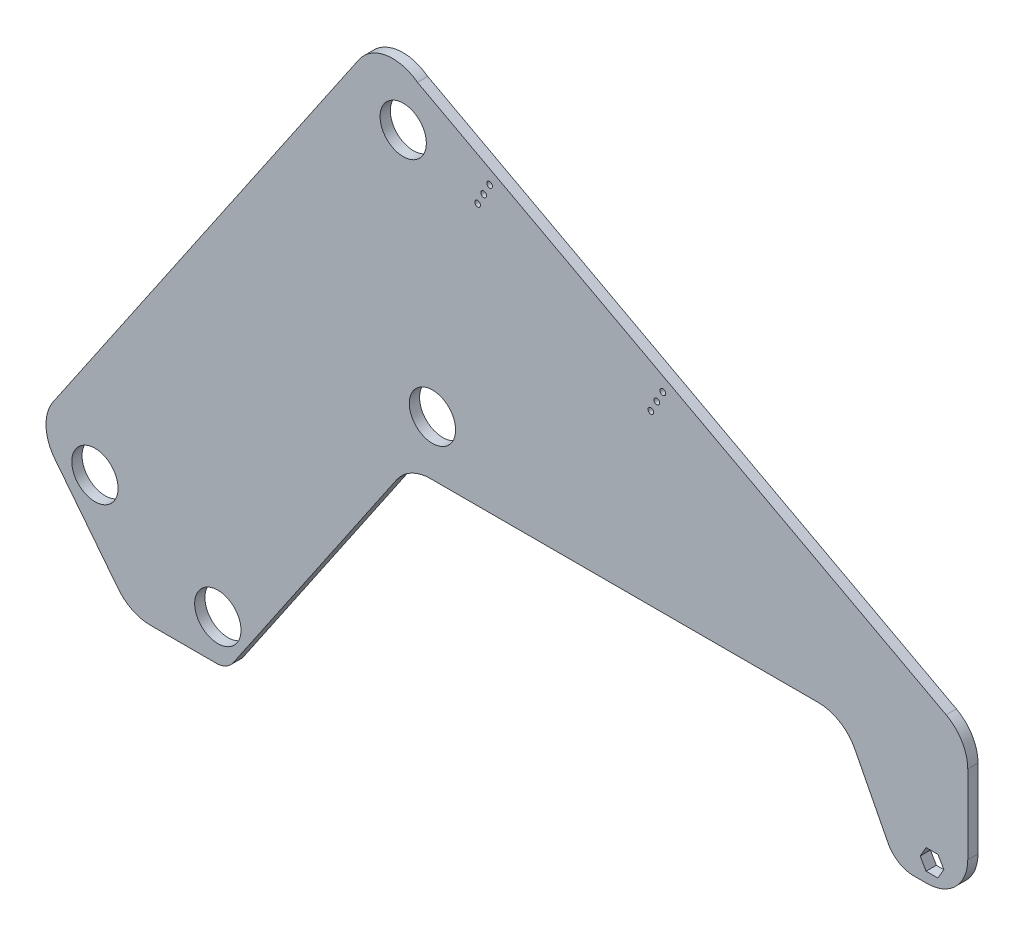
SolidWorks part; units mm, degrees
other "Markup1"
sketch "Sketch1" plane through (-441.7893, 331.8239, 6.35) normal (-0.0431, 0.0102, 0.999) x (0.9985, 0.0354, 0.0427)
sketch "Sketch2" plane through (-413.6701, 343.933, 6.35) normal (-0.0431, 0.0102, 0.999) x (0.9985, 0.0354, 0.0427)
sketch "Sketch3" plane through (-436.3774, 318.5567, 6.35) normal (-0.0431, 0.0102, 0.999) x (0.9985, 0.0354, 0.0427)
sketch "Sketch5" plane through (-436.3774, 318.5567, 6.35) normal (-0.0431, 0.0102, 0.999) x (0.9985, 0.0354, 0.0427)
sketch "Sketch7" plane through (-430.3226, 318.5567, 6.35) normal (-0.0431, 0.0102, 0.999) x (0.9985, 0.0354, 0.0427)
sketch "Sketch9" plane through (-430.3226, 318.5567, 6.35) normal (-0.0431, 0.0102, 0.999) x (0.9985, 0.0354, 0.0427)
sketch "Sketch11" plane through (-430.3226, 318.5567, 6.35) normal (-0.0431, 0.0102, 0.999) x (0.9985, 0.0354, 0.0427)
sketch "Sketch13" plane through (-430.3226, 318.5567, 6.35) normal (-0.0431, 0.0102, 0.999) x (0.9985, 0.0354, 0.0427)
sketch "Sketch15" plane through (-430.3226, 318.5567, 6.35) normal (-0.0431, 0.0102, 0.999) x (0.9985, 0.0354, 0.0427)
sketch "Sketch17" plane through (-430.3226, 318.5567, 6.35) normal (-0.0431, 0.0102, 0.999) x (0.9985, 0.0354, 0.0427)
sketch "Sketch19" plane through (-430.3226, 318.5567, 6.35) normal (-0.0431, 0.0102, 0.999) x (0.9985, 0.0354, 0.0427)
other "Markup2"
sketch "Sketch4" plane through (102.4721, 318.5567, 6.35) normal (0.9364, 0.1073, 0.3342) x (0.3416, -0.0598, -0.9379)
sketch "Sketch6" plane through (102.4721, 318.5567, 6.35) normal (0.9364, 0.1073, 0.3342) x (0.3416, -0.0598, -0.9379)
sketch "Sketch8" plane through (141.2086, 318.5567, 6.35) normal (0.9364, 0.1073, 0.3342) x (0.3416, -0.0598, -0.9379)
sketch "Sketch10" plane through (141.2086, 318.5567, 6.35) normal (0.9364, 0.1073, 0.3342) x (0.3416, -0.0598, -0.9379)
sketch "Sketch12" plane through (141.2086, 318.5567, 6.35) normal (0.9364, 0.1073, 0.3342) x (0.3416, -0.0598, -0.9379)
sketch "Sketch14" plane through (141.2086, 318.5567, 6.35) normal (0.9364, 0.1073, 0.3342) x (0.3416, -0.0598, -0.9379)
sketch "Sketch16" plane through (141.2086, 318.5567, 6.35) normal (0.9364, 0.1073, 0.3342) x (0.3416, -0.0598, -0.9379)
sketch "Sketch18" plane through (141.2086, 318.5567, 6.35) normal (0.9364, 0.1073, 0.3342) x (0.3416, -0.0598, -0.9379)
sketch "Sketch20" plane through (141.2086, 318.5567, 6.35) normal (0.9364, 0.1073, 0.3342) x (0.3416, -0.0598, -0.9379)
material "Lexan"
ref_plane "Front Plane" through (0, 0, 0) normal (0, 0, 1) x (1, 0, 0)
ref_plane "Top Plane" through (0, 0, 0) normal (0, 1, 0) x (1, 0, 0)
ref_plane "Right Plane" through (0, 0, 0) normal (1, 0, 0) x (0, 0, -1)
sketch "Model" plane through (0, 0, 0) normal (0, 0, 1) x (1, 0, 0)
  line L1 (-191.9011, 104.6502) -> (-112.96, 104.6502)
  line L3 (-314.2383, -55.3595) -> (-212.8994, 93.5413)
  line L4 (-236.3032, 307.4477) -> (-425.9209, 28.8361)
  line L5 (-424.8981, -1.1437) -> (-385.5815, -51.2028)
  line L13 (126.3831, 53.8502) -> (122.717, 60.2002)
  line L14 (122.717, 60.2002) -> (115.3846, 60.2002)
  line L15 (115.3846, 60.2002) -> (111.7185, 53.8502)
  line L16 (111.7185, 53.8502) -> (115.3846, 47.5002)
  line L17 (115.3846, 47.5002) -> (122.717, 47.5002)
  line L18 (122.717, 47.5002) -> (126.3831, 53.8502)
  line L19 (-365.606, -60.914) -> (-324.7375, -60.914)
  line L20 (-871.0211, -88.854) -> (370.1019, -88.854) construction
  line L22 (141.2086, 66.5502) -> (141.2086, 78.8846)
  line L27 (107.6196, 41.1502) -> (115.8086, 41.1502)
  line L28 (-399.9752, 2.586) -> (-323.7752, -35.514) construction
  line L29 (-323.7752, -35.514) -> (-190.7071, 138.5169) construction
  line L30 (-190.7071, 138.5169) -> (-208.8329, 283.4378) construction
  line L31 (-208.8329, 283.4378) -> (-399.9752, 2.586) construction
  line L32 (91.8004, 50.8135) -> (71.26, 90.8456)
  line L33 (48.6612, 104.6502) -> (-11.3966, 104.6502)
  line L34 (141.2086, 78.8846) -> (141.2086, 115.3033)
  line L35 (127.8091, 137.6897) -> (-86.3327, 252.4836)
  line L36 (-112.96, 104.6502) -> (-68.51, 104.6502)
  line L37 (-122.3008, 271.7648) -> (-85.2777, 251.9181)
  line L38 (-199.9496, 313.3896) -> (-46.986, 224.7627)
  line L39 (-46.986, 224.7627) -> (-44.2259, 229.9116)
  line L40 (-68.51, 104.6502) -> (-2.1388, 104.6502)
  line L41 (-122.3008, 271.7648) -> (-199.9496, 313.3896)
  line L42 (-51.0757, 217.1337) -> (-46.986, 224.7627)
  line L43 (-47.826, 223.1957) -> (-51.5462, 216.2559) construction
  line L44 (-199.9496, 313.3896) -> (-154.405, 282.3463)
  line L45 (-154.405, 282.3463) -> (-151.6449, 287.4952)
  line L46 (-154.405, 282.3463) -> (-156.7821, 277.912)
  line L47 (-155.2451, 280.7793) -> (-158.9652, 273.8395) construction
  arc A3 (121.2475, 59.8082) -> (121.352, 60.2002) centre (96.7586, 66.5502) ccw
  circle A9 centre (-323.7752, -35.514) radius 14.351
  circle A10 centre (-399.9752, 2.586) radius 14.351
  circle A12 centre (-190.7071, 138.5169) radius 14.351
  arc A15 (107.6196, 41.1502) -> (91.8004, 50.8135) centre (107.6196, 58.9302) cw
  arc A21 (-191.9011, 104.6502) -> (-212.8994, 93.5413) centre (-191.9011, 79.2502) ccw
  circle A22 centre (-208.8329, 283.4378) radius 14.351
  circle A24 centre (119.0508, 53.8502) radius 6.35 construction
  arc A31 (-324.7375, -60.914) -> (-314.2383, -55.3595) centre (-324.7375, -48.214) ccw
  arc A40 (114.7422, 48.6129) -> (115.0458, 48.9225) centre (96.7586, 66.5502) ccw
  arc A43 (115.8086, 41.1502) -> (141.2086, 66.5502) centre (115.8086, 66.5502) ccw
  arc A44 (-236.3032, 307.4477) -> (-199.9496, 313.3896) centre (-215.305, 293.1567) cw
  arc A45 (-365.606, -60.914) -> (-385.5815, -51.2028) centre (-365.606, -35.514) cw
  arc A46 (71.26, 90.8456) -> (48.6612, 104.6502) centre (48.6612, 79.2502) ccw
  arc A47 (141.2086, 115.3033) -> (127.8091, 137.6897) centre (115.8086, 115.3033) ccw
  arc A48 (-424.8981, -1.1437) -> (-425.9209, 28.8361) centre (-404.9226, 14.5451) cw
  circle A50 centre (-47.826, 223.1957) radius 1.778
  circle A51 centre (-51.5462, 216.2559) radius 1.778
  circle A52 centre (-55.2664, 209.3162) radius 1.778
  circle A53 centre (-155.2451, 280.7793) radius 1.778
  circle A54 centre (-158.9652, 273.8395) radius 1.778
  circle A55 centre (-162.6854, 266.8998) radius 1.778
  ellipse E0 centre (-551.1692, 173.9527) end of major axis (-591.2054, 216.0961) minor radius 17.278
  point P31 (-177.5612, 330.9695)
  point P34 (100.2935, -12.8222)
  point P43 (-377.9543, -60.914)
  point P55 (96.7586, 41.1502)
  point P59 (174.831, 53.8502)
  point P60 (-205.3388, 104.6502)
  point P64 (-436.3774, 13.472)
  dimension "D3" = 38.1
  dimension "D4" = 104.6502
  dimension "D5" = 76.2
  dimension "D6" = 44.45
  dimension "D7" = 12.7
  dimension "D8" = 28.702
  dimension "D11" = 139.7
  dimension "D12" = 27.94
  dimension "D21" = 124.238
  dimension "D13" = 12.7
  dimension "D16" = 355.6
  dimension "D23" = 25.4
  dimension "D24" = 25.4
  dimension "D26" = 25.4
  dimension "D14" = 406.4
  dimension "D20" = 254
  dimension "D29" = 25.4
  dimension "D31" = 25.4
  dimension "D25" = 88.9
  dimension "D30" = 17.78
  dimension "D32" = 25.4
  dimension "D33" = 25.4
  dimension "D34" = 176.784
  dimension "D35" = 5.842
  dimension "D37" = 3
  dimension "D38" = 7.874
  dimension "D36" = 3.556
  dimension "D41" = 3.556
  dimension "D9" = 19.05
  dimension "D10" = 146.05
  dimension "D15" = 33.8667
  dimension "D17" = 339.725
  dimension "D18" = 219.075
  dimension "D19" = 50.8
  dimension "D22" = 25.4
  dimension "D27" = 53.2168
  dimension "D28" = 12.7
  dimension "D39" = 5.842
  dimension "D40" = 55.118
  dimension "D43" = 7.874
  dimension "D42" = 3
extrude "Boss-Extrude1" add sketch "Model" along normal blind 6.35 contours A51 A50 L38 A44 L4 A48 L5 A45 L19 A31 L3 A21 L1 L36 L40 L33 A46 L32 A15 L27 A43 L22 L34 A47 L35 L39 A52 A22 A12 A10 A9 L18 L17 L16 L15 L14 L13 | L37 L41 L38 L39 L35 | L44 L45 L38 | L38 L45 L41 region at (-206.9871, 107.7659, 0) region at (-168.0319, 295.5943, 0) region at (-168.9519, 293.878, 0) region at (-89.4971, 251.8082, 0)
